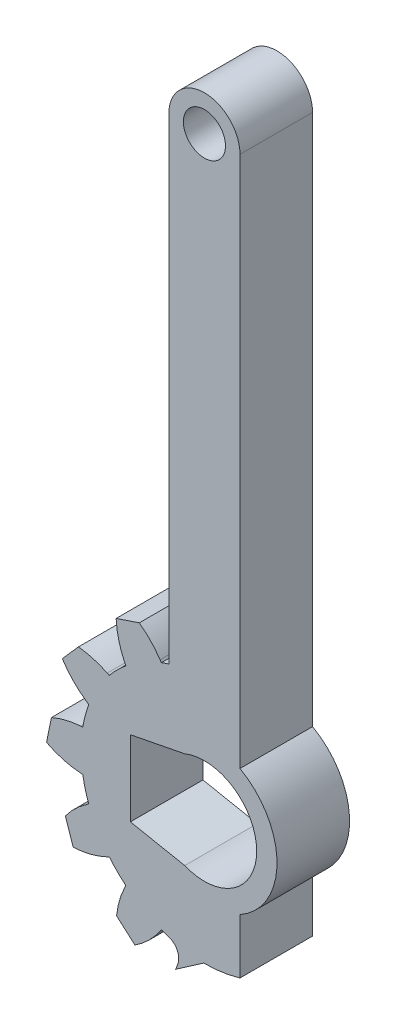
SolidWorks part; units mm, degrees
ref_plane "Front Plane" through (0, 0, 0) normal (0, 0, 1) x (1, 0, 0)
ref_plane "Top Plane" through (0, 0, 0) normal (0, 1, 0) x (1, 0, 0)
ref_plane "Right Plane" through (0, 0, 0) normal (1, 0, 0) x (0, 0, -1)
ref_plane "Plane1" through (0, 0, 1.9) normal (0, 0, 1) x (1, 0, 0)
sketch "Sketch1" plane through (0, 0, 1.9) normal (0, 0, 1) x (1, 0, 0)
  line L0 (2.45, -8.1393) -> (2.45, -4.3586)
  line L1 (2.45, 4.3586) -> (2.45, 41)
  line L2 (-2.45, 41) -> (-2.45, 8.1393)
  line L3 (-2.9677, 7.9651) -> (-3.0542, 8.0933)
  line L4 (-5.4819, 6.6916) -> (-5.4141, 6.5527)
  line L5 (-6.5527, 5.4141) -> (-6.6916, 5.4819)
  line L6 (-8.0933, 3.0542) -> (-7.9651, 2.9677)
  line L7 (-8.3818, 1.4124) -> (-8.5361, 1.4016)
  line L8 (-8.5361, -1.4016) -> (-8.3818, -1.4124)
  line L9 (-7.9651, -2.9677) -> (-8.0933, -3.0542)
  line L10 (-6.6916, -5.4819) -> (-6.5527, -5.4141)
  line L11 (-5.4141, -6.5527) -> (-5.4819, -6.6916)
  line L12 (-3.0542, -8.0933) -> (-2.9677, -7.9651)
  line L13 (-1.4371, -8.3776) -> (-1.9842, -9.839)
  line L17 (-1.9842, -9.839) -> (-0.053, -8.4998)
  arc A0 (2.45, -4.3586) -> (2.45, 4.3586) centre (0, 0) ccw
  arc A1 (2.45, 41) -> (-2.45, 41) centre (0, 41) ccw
  arc A2 (-2.45, 8.1393) -> (-2.9677, 7.9651) centre (0, 0) ccw
  arc A3 (-3.0542, 8.0933) -> (-5.9946, 10.3829) centre (-8.0284, 4.7381) ccw
  arc A4 (-5.9946, 10.3829) -> (-5.4819, 6.6916) centre (-0.0891, 9.3218) ccw
  arc A5 (-5.4141, 6.5527) -> (-6.5527, 5.4141) centre (0, 0) ccw
  arc A6 (-6.6916, 5.4819) -> (-10.3829, 5.9946) centre (-9.3218, 0.0891) ccw
  arc A7 (-10.3829, 5.9946) -> (-8.0933, 3.0542) centre (-4.7381, 8.0284) ccw
  arc A8 (-7.9651, 2.9677) -> (-8.3818, 1.4124) centre (0, 0) ccw
  arc A9 (-8.5361, 1.4016) -> (-11.9891, 0) centre (-8.1175, -4.5837) ccw
  arc A10 (-11.9891, 0) -> (-8.5361, -1.4016) centre (-8.1175, 4.5837) ccw
  arc A11 (-8.3818, -1.4124) -> (-7.9651, -2.9677) centre (0, 0) ccw
  arc A12 (-8.0933, -3.0542) -> (-10.3829, -5.9946) centre (-4.7381, -8.0284) ccw
  arc A13 (-10.3829, -5.9946) -> (-6.6916, -5.4819) centre (-9.3218, -0.0891) ccw
  arc A14 (-6.5527, -5.4141) -> (-5.4141, -6.5527) centre (0, 0) ccw
  arc A15 (-5.4819, -6.6916) -> (-5.9946, -10.3829) centre (-0.0891, -9.3218) ccw
  arc A16 (-5.9946, -10.3829) -> (-3.0542, -8.0933) centre (-8.0284, -4.7381) ccw
  arc A17 (-2.9677, -7.9651) -> (-1.4371, -8.3776) centre (0, 0) ccw
  circle A18 centre (0, 41) radius 1.45
  arc A19 (-2.45, 8.1393) -> (-1.4371, -8.3776) centre (0, 0) cw construction
  arc A22 (-0.053, -8.4998) -> (2.45, -8.1393) centre (0, 0) ccw
  dimension "D1" = 5
  dimension "D2" = 0.0891
  dimension "D3" = 8.5
  dimension "D4" = 6
  dimension "D13" = 2.9
  dimension "D14" = 34.736
  dimension "D17" = 0.053
  dimension "D18" = 1.4371
  dimension "D19" = 1.9842
  dimension "D5" = 2.9677
  dimension "D6" = 3.0542
  dimension "D7" = 4.7381
  dimension "D8" = 5.4141
  dimension "D9" = 5.4819
  dimension "D10" = 6.5527
  dimension "D11" = 8.1175
  dimension "D12" = 8.3818
  dimension "D15" = 41
  dimension "4,9" = 4.9
extrude "Boss-Extrude1" add sketch "Sketch1" against normal blind 5
ref_plane "Plane2" through (0, 0, 1.9) normal (0, 0, -1) x (-1, 0, 0)
sketch "Sketch4" plane through (0, 0, 1.9) normal (0, 0, 1) x (1, 0, 0)
  line L0 (-5.1029, -2.6) -> (-1.3588, -3.3337)
  line L1 (-1.3588, 3.3337) -> (-5.1029, 2.6)
  line L2 (-5.1029, 2.6) -> (-5.1029, -2.6)
  arc A0 (-1.3588, -3.3337) -> (-1.3588, 3.3337) centre (0, 0) cw
extrude "Cut-Extrude2" cut sketch "Sketch4" against normal through all
sketch "Sketch5" plane through (0, 0, 0) normal (0, 1, 0) x (1, 0, 0)
  line L0 (3.6, 3.1) -> (0, 3.1)
  line L1 (0, 3.1) -> (0, -1.9)
  line L2 (0, -1.9) -> (3.6, -1.9)
  line L3 (3.6, -1.9) -> (3.6, 3.1)
  line L4 (0, 3.1) -> (0, -1.9) construction
  line L5 (2.45, 3.1) -> (-2.45, 3.1) construction
revolve "Cut-Revolve1" cut sketch "Sketch5" angle 360 about L4 reverse direction yes
chamfer "Chamfer1" distance 1.4124 angle 61.288 5 edges at (-10.3829, -5.9946, -0.6) (-5.9946, -10.3829, -0.6) (-11.9891, 0, -0.6) (-10.3829, 5.9946, -0.6) (-5.9946, 10.3829, -0.6) first distance on face at (-8.5169, -5.8852, -0.6) first distance on face at (-4.4332, -9.3551, -0.6) first distance on face at (-10.3184, -0.8383, -0.6) first distance on face at (-9.3551, 4.4332, -0.6) first distance on face at (-5.8852, 8.5169, -0.6)
fillet "Fillet1" radius 1 1 edges at (-1.4371, -8.3776, -0.6) tangent propagation no
